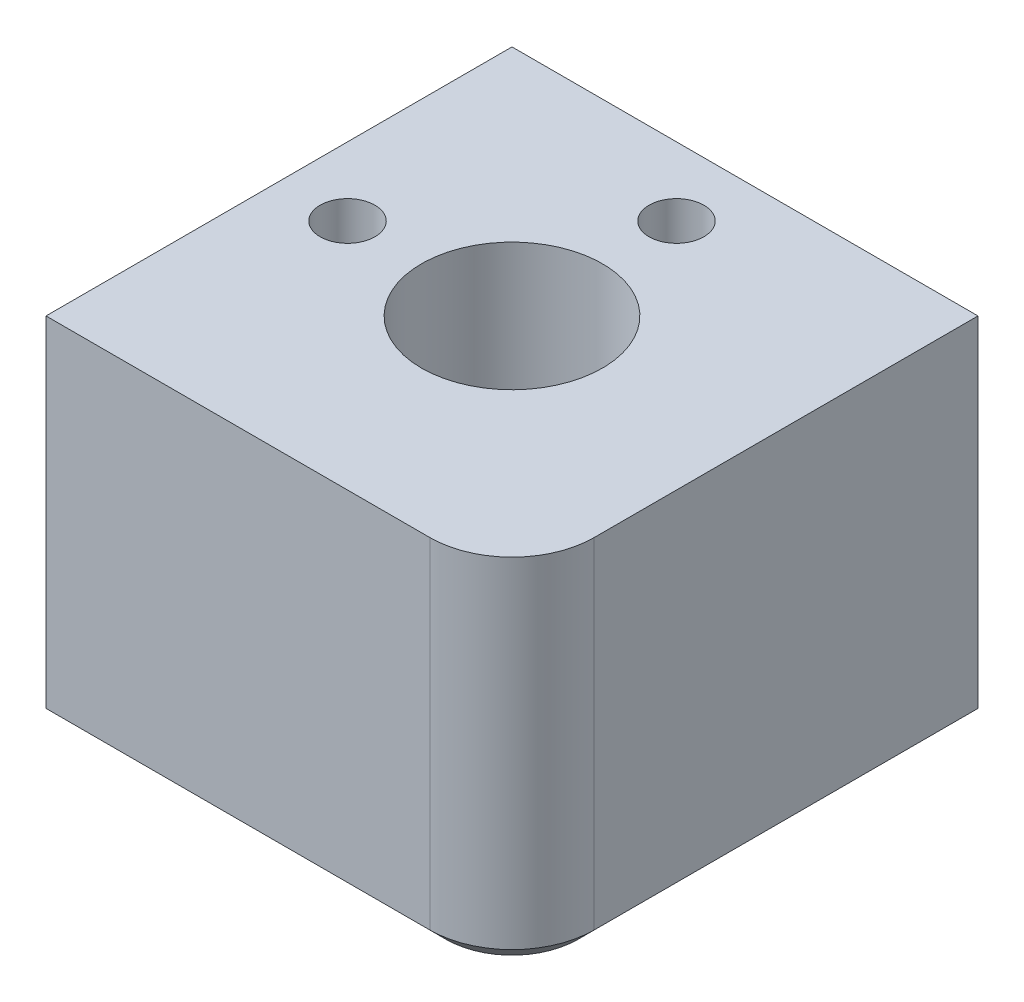
SolidWorks part; units mm, degrees
material "6061-T6 (SS)"
ref_plane "Front Plane" through (0, 0, 0) normal (0, 0, 1) x (1, 0, 0)
ref_plane "Top Plane" through (0, 0, 0) normal (0, 1, 0) x (1, 0, 0)
ref_plane "Right Plane" through (0, 0, 0) normal (1, 0, 0) x (0, 0, -1)
sketch "Base" plane through (0, 0, 0) normal (0, 1, 0) x (1, 0, 0)
  line L1 (-4.25, -4.25) -> (4.25, -4.25)
  line L2 (-4.25, -4.25) -> (-4.25, 4.25)
  line L3 (-4.25, 4.25) -> (4.25, 4.25)
  line L4 (4.25, -4.25) -> (4.25, 4.25)
  line L5 (-4.25, -4.25) -> (4.25, 4.25) construction
  line L6 (-4.25, 4.25) -> (4.25, -4.25) construction
  point P0 (0, 0)
  dimension "D1" = 8.5
  dimension "D2" = 8.5
extrude "Boss-Extrude1" add sketch "Base" against normal blind 8
sketch "Cutout" plane through (0, 0, 0) normal (0, 1, 0) x (1, 0, 0)
  line L1 (-4.25, 4.25) -> (2.75, 4.25)
  line L2 (-4.25, 4.25) -> (-4.25, -2.75)
  line L3 (-4.25, -2.75) -> (2.75, -2.75)
  line L4 (2.75, 4.25) -> (2.75, -2.75)
  line L5 (2.75, -2.75) -> (-4.25, 4.25) construction
  line L6 (2.75, 4.25) -> (-4.25, -2.75) construction
  point P5 (-0.75, 0.75)
  dimension "D1" = 7
  dimension "D2" = 7
extrude "Cut-Extrude1" cut sketch "Cutout" against normal blind 1.5
sketch "Sketch3" plane through (2.75, 0, 0) normal (-1, 0, 0) x (0, 0, 1)
  line L0 (2.75, -1.5) -> (-4.25, -1.5) construction
  line L1 (-4.25, 0) -> (-2.75, 0)
  line L2 (-4.25, 0) -> (-4.25, -1.5)
  line L3 (-4.25, -1.5) -> (-2.75, -1.5)
  line L4 (-2.75, 0) -> (-2.75, -1.5)
  dimension "D1" = 1.5
extrude "Cut-Extrude2" cut sketch "Sketch3" against normal through all
ref_axis "Axis2" through (2.75, -1.5, 2.75) along (-0.7071, 0, -0.7071)
ref_plane "Plane1" through (0, 0, 0) normal (0.7071, 0, -0.7071) x (-0.7071, 0, -0.7071)
mirror "Mirror1" about plane through (0, 0, 0) normal (0.7071, 0, -0.7071) of "Cut-Extrude2"
fillet "Fillet3" radius 0.508 1 edges at (2.75, -0.75, 2.75)
fillet "Fillet4" radius 1.5 1 edges at (4.25, -4, 4.25)
hole_wizard "M4 Tapped Hole1" positions "Sketch12" profile "Sketch13" tap size "M4" standard "AS" end condition through all
sketch "Sketch12" plane through (0, -1.5, 0) normal (0, 1, 0) x (1, 0, 0)
  line L3 (4.25, -2.75) -> (4.25, 2.75) construction
  line L4 (-2.75, -4.25) -> (2.75, -4.25) construction
  point P0 (0, 0)
  dimension "D1" = 4.25
  dimension "D2" = 4.25
cosmetic thread "Hole Thread1" parameters "D2"=4
sketch "Sketch13" plane through (0, -1.5, 0) normal (1, 0, 0) x (0, 0, 1)
  line L0 (0, 0) -> (0, 6.5)
  line L1 (0, 6.5) -> (1.65, 6.5)
  line L2 (1.65, 6.5) -> (1.65, 0)
  line L5 (1.65, 0) -> (0, 0)
  line L11 (0, -6.35) -> (0, 107.95) construction
  dimension "Thru Tap Drill Dia." = 3.3
  dimension "Thru Tap Drill Depth" = 6.5
chamfer "Chamfer1" distance 0.3 angle 45 5 edges at (-4.25, -8, 0) (-0.75, -8, 4.25) (3.8107, -8, 3.8107) (4.25, -8, -0.75) (0, -8, -4.25)
sketch "Sketch14" plane through (0, 0, 0) normal (0, 1, 0) x (1, 0, 0)
  line L6 (-2.75, -4.25) -> (2.75, -4.25)
  line L7 (4.25, -2.75) -> (4.25, 2.75)
  line L8 (4.25, 2.75) -> (2.75, 2.75)
  line L9 (2.75, 2.75) -> (2.75, -2.242)
  line L10 (2.242, -2.75) -> (-2.75, -2.75)
  line L11 (-2.75, -2.75) -> (-2.75, -4.25)
  line L12 (-2.75, -4.25) -> (2.75, -4.25)
  line L13 (4.25, -2.75) -> (4.25, 2.75)
  line L14 (4.25, 2.75) -> (2.75, 2.75)
  line L15 (2.75, 2.75) -> (2.75, -2.242)
  line L16 (2.242, -2.75) -> (-2.75, -2.75)
  line L17 (-2.75, -2.75) -> (-2.75, -4.25)
  arc A2 (2.75, -4.25) -> (4.25, -2.75) centre (2.75, -2.75) ccw
  arc A3 (2.242, -2.75) -> (2.75, -2.242) centre (2.242, -2.242) ccw
  arc A4 (2.75, -4.25) -> (4.25, -2.75) centre (2.75, -2.75) ccw
  arc A5 (2.242, -2.75) -> (2.75, -2.242) centre (2.242, -2.242) ccw
  dimension "D1" = 0
extrude "Cut-Extrude3" cut sketch "Sketch14" against normal up to surface (1.5 mm away) up to face at (0, -1.5, 1.65)
sketch "Sketch15" plane through (0, -1.5, 0) normal (0, 1, 0) x (1, 0, 0)
  line L0 (0, 4.25) -> (0, 0) construction
  line L1 (4.25, 4.25) -> (-4.25, 4.25) construction
  line L2 (0, 0) -> (-4.25, 0) construction
  line L3 (-4.25, 4.25) -> (-4.25, -4.25) construction
  circle A0 centre (0, 3) radius 0.5
  circle A1 centre (-3, 0) radius 0.5
  dimension "D1" = 1
  dimension "D2" = 1.25
  dimension "D3" = 1.25
extrude "Cut-Extrude4" cut sketch "Sketch15" against normal blind 2.54
